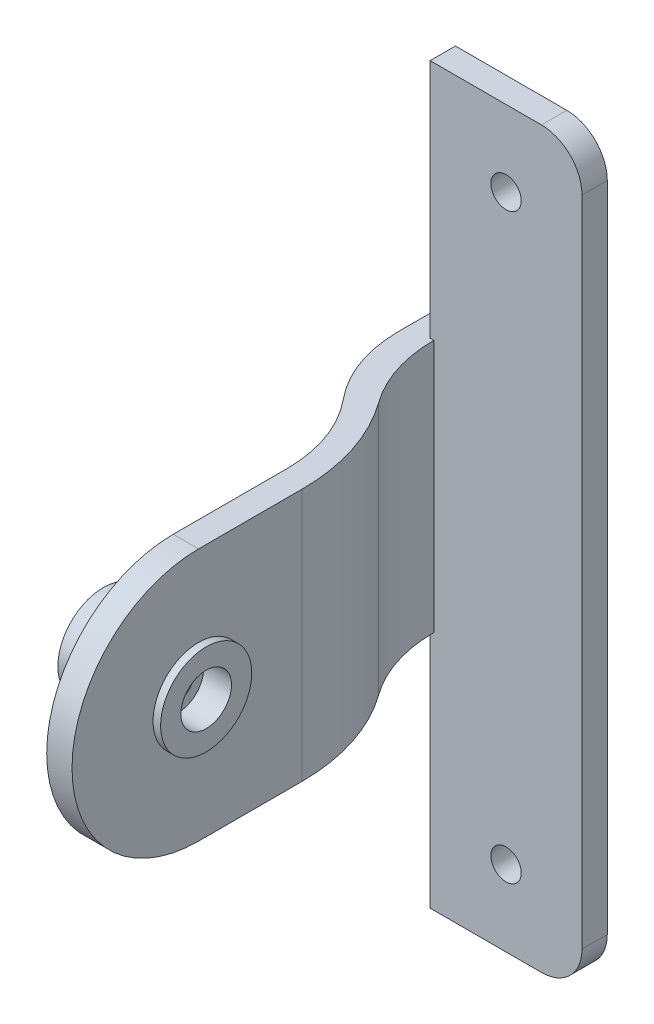
SolidWorks part; units mm, degrees
ref_plane "Front Plane" through (0, 0, 0) normal (0, 0, 1) x (1, 0, 0)
ref_plane "Top Plane" through (0, 0, 0) normal (0, 1, 0) x (1, 0, 0)
ref_plane "Right Plane" through (0, 0, 0) normal (1, 0, 0) x (0, 0, -1)
sketch "Sketch1" plane through (0, 0, 0) normal (1, 0, 0) x (0, 0, -1)
  line L1 (0, 12.5) -> (34.45, 12.5)
  line L2 (0, 1.5) -> (0, -12.5)
  line L3 (0, -12.5) -> (34.45, -12.5)
  line L4 (34.45, 12.5) -> (34.45, -12.5)
  circle A0 centre (0, 0) radius 1.5
  circle A1 centre (0, 0) radius 12.5 construction
  arc A2 (0, 12.5) -> (0, -12.5) centre (0, 0) ccw
  dimension "D1" = 3
  dimension "D2" = 25
  dimension "D3" = 34.45
extrude "Boss-Extrude1" add sketch "Sketch1" along normal blind 2.5 contours L1 A2 A0 L3 L4 region at (0, 0, -12.3069)
sketch "Sketch2" plane through (0, 0, 0) normal (-1, 0, 0) x (0, 0, 1)
  circle A0 centre (0, 0) radius 1.5
  circle A1 centre (0, 0) radius 4.5
  dimension "D1" = 9
  dimension "D2" = 3
extrude "Boss-Extrude2" add sketch "Sketch2" along normal blind 6.9 and the other way offset from surface 0.75 other way up to face at (2.5, 0, -14.1)
sketch "Sketch4" plane through (2.5, 0, 0) normal (1, 0, 0) x (0, 0, -1)
  circle A0 centre (0, 0) radius 2.5
extrude "Cut-Extrude1" cut sketch "Sketch4" against normal blind 2
sketch "Sketch5" plane through (2.5, 0, 0) normal (1, 0, 0) x (0, 0, -1)
  circle A0 centre (0, 0) radius 4.5
  circle A1 centre (0, 0) radius 2.5
  dimension "D1" = 9
  dimension "D2" = 5
extrude "Boss-Extrude3" add sketch "Sketch5" along normal blind 0.75
sketch "Sketch6" plane through (0, 0, -34.45) normal (0, 0, -1) x (-1, 0, 0)
  line L1 (-8.8125, 36.25) -> (53.3216, 36.25)
  line L3 (6.25, -36.25) -> (53.3216, -36.25)
  line L4 (53.3216, 36.25) -> (53.3216, -36.25)
  line L6 (53.3216, -36.25) -> (-19.1784, 36.25) construction
  line L7 (6.25, -36.25) -> (-19.1784, -36.25)
  line L9 (-8.8125, 36.25) -> (-19.1784, 36.25)
  line L10 (-19.1784, -36.25) -> (-19.1784, 36.25)
  line L11 (53.3216, 36.25) -> (-19.1784, -36.25) construction
  point P4 (17.0716, 0)
  dimension "D1" = 72.5
  dimension "D2" = 72.5
extrude "Boss-Extrude4" add sketch "Sketch6" against normal blind 2.5
ref_plane "Plane1" through (-17.0716, 0, 0) normal (1, 0, 0) x (0, 0, -1)
ref_plane "Plane2" through (9.4784, 0, 0) normal (1, 0, 0) x (0, 0, -1)
sketch "Sketch7" plane through (0, 0, -31.95) normal (0, 0, 1) x (1, 0, 0)
  line L7 (1.7881, -3.3824) -> (-5.2119, -3.3824)
  line L12 (1.7881, -3.3824) -> (1.7881, -19.8824)
  line L18 (1.7881, -19.8824) -> (-5.2119, -19.8824)
  line L19 (-5.2119, -3.3824) -> (-5.2119, -19.8824)
  line L20 (1.7881, -3.3824) -> (-5.2119, -19.8824) construction
  line L21 (1.7881, -19.8824) -> (-5.2119, -3.3824) construction
  line L22 (-24.5, -4) -> (-8.5, -4)
  line L23 (-24.5, -4) -> (-24.5, 4)
  line L24 (-24.5, 4) -> (-8.5, 4)
  line L25 (-8.5, -4) -> (-8.5, 4)
  line L26 (-24.5, -4) -> (-8.5, 4) construction
  line L27 (-24.5, 4) -> (-8.5, -4) construction
  point P0 (-16.5, 0)
  point P2 (-1.7119, -11.6324)
  dimension "D1" = 16
  dimension "D2" = 16.5
  dimension "D3" = 7
  dimension "D4" = 8
extrude "Cut-Extrude2" cut sketch "Sketch7" against normal up to next
sketch "Sketch8" plane through (0, 0, 0) normal (0, 1, 0) x (1, 0, 0)
  line L13 (0, 7.7296) -> (2.5, 7.7296)
  line L17 (0, 11.2296) -> (0, 7.7296)
  line L18 (-3.7212, 31.95) -> (-3.7212, 29.45)
  line L19 (-6.2212, 31.95) -> (-6.2212, 28.45)
  line L20 (-6.2212, 31.95) -> (-3.7212, 31.95)
  line L22 (2.5, 7.7296) -> (2.5, 10.2296)
  line L23 (2.5, 0) -> (2.5, 31.95) construction
  line L24 (0, 0) -> (0, 31.95) construction
  line L25 (0, -13.75) -> (0, 13.75) construction
  line L26 (-53.3216, 31.95) -> (19.1784, 31.95) construction
  line L27 (19.1784, 31.95) -> (19.1784, 34.45) construction
  arc A5 (-1.1155, 21.3996) -> (2.5, 10.2296) centre (-16.5626, 10.2296) cw
  arc A6 (-3.1485, 19.9446) -> (-6.2212, 28.45) centre (7.0867, 28.45) cw
  arc A7 (-3.1485, 19.9446) -> (0, 11.2296) centre (-13.636, 11.2296) cw
  arc A8 (-3.7212, 29.45) -> (-1.1155, 21.3996) centre (10.0176, 29.45) ccw
  dimension "D3" = 22.8996
  dimension "D4" = 3.5
  dimension "D1" = 2.5
  dimension "D2" = 2.5
  dimension "D5" = 3.5
  dimension "D6" = 2.5
  dimension "D7" = 2.5
sketch "Sketch9" plane through (0, -12.5, 0) normal (0, -1, 0) x (1, 0, 0)
  line L0 (2.5, 0) -> (2.5, -31.95) construction
  line L1 (0, -31.95) -> (2.5, -31.95)
  line L2 (0, -31.95) -> (0, -9.5612)
  line L3 (0, -9.5612) -> (2.5, -9.5612)
  line L4 (2.5, -31.95) -> (2.5, -9.5612)
extrude "Cut-Extrude3" cut sketch "Sketch9" against normal up to next
extrude "Boss-Extrude5" add sketch "Sketch8" along normal mid plane 25
fillet "Fillet1" [suppressed] radius 4
fillet "Fillet2" radius 1 8 edges at (-5.2119, -3.3824, -33.2) (-5.2119, -19.8824, -33.2) (1.7881, -3.3824, -33.2) (-8.5, 4, -33.2) (1.7881, -19.8824, -33.2) (-8.5, -4, -33.2) (-24.5, 4, -33.2) (-24.5, -4, -33.2)
fillet "Fillet3" radius 4 4 edges at (19.1784, -36.25, -33.2) (19.1784, 36.25, -33.2) (-53.3216, 36.25, -33.2) (-53.3216, -36.25, -33.2)
sketch "Sketch10" plane through (0, 0, 0) normal (0, 1, 0) x (1, 0, 0)
  line L0 (15.1784, 31.95) -> (19.1784, 31.95) construction
  line L1 (21.7259, 31.95) -> (-56.5098, 31.95)
  line L2 (21.7259, 31.95) -> (21.7259, 38.24)
  line L3 (21.7259, 38.24) -> (-56.5098, 38.24)
  line L4 (-56.5098, 31.95) -> (-56.5098, 38.24)
extrude "Cut-Extrude4" cut sketch "Sketch10" against normal through all both and the other way through all
sketch "Sketch11" plane through (0, 0, 0) normal (0, 1, 0) x (1, 0, 0)
  line L0 (-3.7212, 29.45) -> (-3.7212, 31.95) construction
  line L1 (10.9188, 31.95) -> (-3.7212, 31.95)
  line L2 (10.9188, 31.95) -> (10.9188, 29.45)
  line L3 (10.9188, 29.45) -> (-3.7212, 29.45)
  line L4 (-3.7212, 31.95) -> (-3.7212, 29.45)
  line L5 (-3.7212, 31.95) -> (-6.2212, 31.95) construction
  dimension "D1" = 2.5
  dimension "D2" = 14.64
extrude "Boss-Extrude6" add sketch "Sketch11" along normal mid plane 25
sketch "Sketch12" plane through (0, 0, -31.95) normal (0, 0, -1) x (-1, 0, 0)
  line L0 (5.5825, 0) -> (-5.5825, 0) construction
  line L1 (-10.9188, 36.25) -> (61.5812, 36.25) construction
  line L2 (-10.9188, 36.25) -> (-10.9188, -36.25) construction
  line L3 (-10.9188, -36.25) -> (61.5812, -36.25) construction
  line L4 (61.5812, 36.25) -> (61.5812, -36.25) construction
  line L5 (-10.9188, 36.25) -> (61.5812, -36.25) construction
  line L6 (61.5812, 36.25) -> (-10.9188, -36.25) construction
  line L7 (-10.9188, 12.5) -> (-10.9188, -12.5) construction
  circle A0 centre (-3.4188, 28.75) radius 1.5
  circle A1 centre (-3.4188, -28.75) radius 1.5
  circle A2 centre (-3.4188, 28.75) radius 3
  circle A3 centre (-3.4188, -28.75) radius 3
  point P4 (-10.9188, 0)
  dimension "D3" = 3
  dimension "D5" = 6
  dimension "D1" = 72.5
  dimension "D2" = 72.5
  dimension "D4" = 7.5
sketch "Sketch13" plane through (0, 0, -31.95) normal (0, 0, -1) x (-1, 0, 0)
  line L1 (-10.9188, 12.5) -> (4.0812, 12.5)
  line L2 (-10.9188, 12.5) -> (-10.9188, 28.75)
  line L4 (4.0812, 12.5) -> (4.0812, 28.75)
  line L5 (-3.6788, 36.25) -> (-6.9188, 36.25)
  line L6 (-10.9188, 32.25) -> (-10.9188, 28.75)
  line L7 (4.0812, 28.75) -> (4.0812, 36.25)
  line L8 (4.0812, 36.25) -> (-3.6788, 36.25)
  arc A1 (-6.9188, 36.25) -> (-10.9188, 32.25) centre (-6.9188, 32.25) ccw
  point P7 (0, 0)
  dimension "D2" = 4
  dimension "D1" = 7.5
extrude "Boss-Extrude7" add sketch "Sketch13" against normal blind 2.5
mirror "Mirror1" about plane through (0, 0, 0) normal (0, 1, 0) of "Boss-Extrude6", "Boss-Extrude7"
sketch "Sketch14" plane through (0, 0, -31.95) normal (0, 0, -1) x (-1, 0, 0)
  line L0 (4.0812, 36.25) -> (-6.9188, 36.25) construction
  line L1 (4.0812, 12.5) -> (4.0812, 36.25) construction
  circle A0 centre (-3.4188, 28.75) radius 1.5
  dimension "D1" = 7.5
  dimension "D2" = 7.5
extrude "Cut-Extrude5" cut sketch "Sketch14" against normal blind 2.5
sketch "Sketch15" plane through (0, 0, -31.95) normal (0, 0, -1) x (-1, 0, 0)
  circle A0 centre (-3.4188, 28.75) radius 2.5
  circle A1 centre (-3.4188, 28.75) radius 4
  dimension "D1" = 8
  dimension "D2" = 5
extrude "Boss-Extrude8" [suppressed] add sketch "Sketch15" against normal blind 6
mirror "Mirror2" about plane through (0, 0, 0) normal (0, 1, 0) of "Cut-Extrude5", "Boss-Extrude8"
